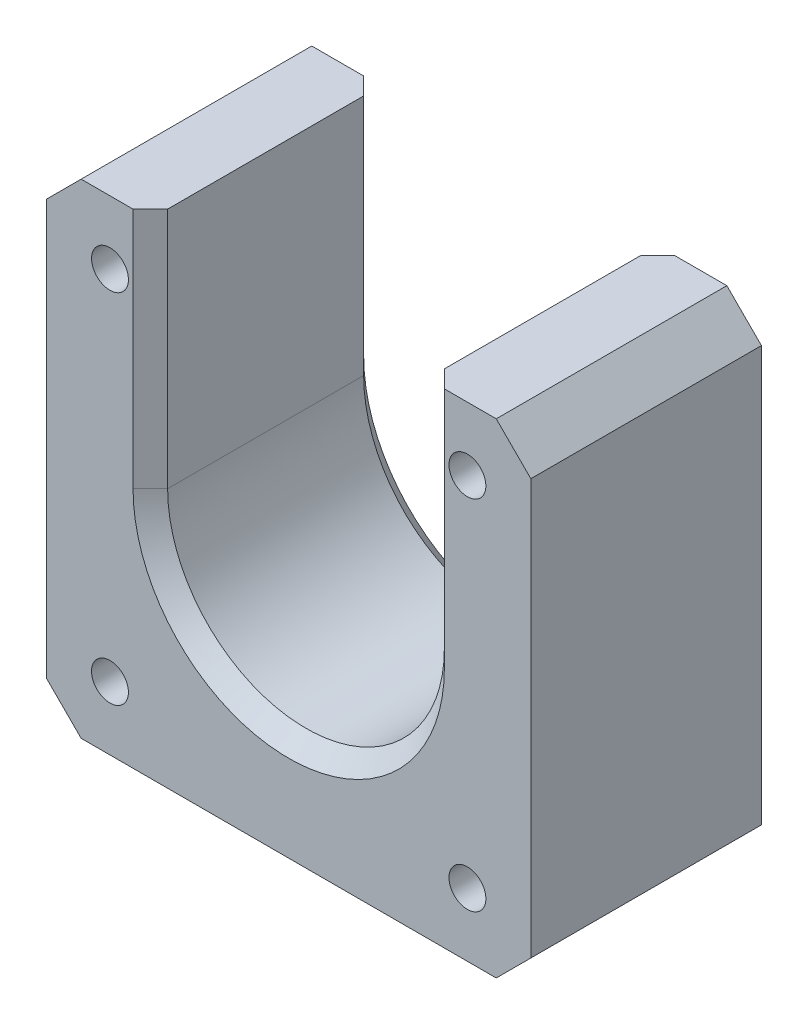
SolidWorks part; units mm, degrees
ref_plane "Front Plane" through (0, 0, 0) normal (0, 0, 1) x (1, 0, 0)
ref_plane "Top Plane" through (0, 0, 0) normal (0, 1, 0) x (1, 0, 0)
ref_plane "Right Plane" through (0, 0, 0) normal (1, 0, 0) x (0, 0, -1)
sketch "Sketch1" plane through (0, 0, 0) normal (0, 0, 1) x (1, 0, 0)
  line L1 (-21, 21) -> (21, 21)
  line L2 (-21, 21) -> (-21, -21)
  line L3 (-21, -21) -> (21, -21)
  line L4 (21, 21) -> (21, -21)
extrude "Boss-Extrude1" add sketch "Sketch1" along normal blind 20
sketch "Sketch2" plane through (0, 0, 20) normal (0, 0, 1) x (1, 0, 0)
  line L0 (-12, 0) -> (-12, 21)
  line L1 (-12, 21) -> (12, 21)
  line L2 (12, 21) -> (12, 0)
  circle A0 centre (-15.5, 15.5) radius 1.6
  circle A1 centre (15.5, -15.5) radius 1.6
  circle A3 centre (15.5, 15.5) radius 1.6
  circle A4 centre (-15.5, -15.5) radius 1.6
  arc A5 (-12, 0) -> (12, 0) centre (0, 0) ccw
extrude "Cut-Extrude1" cut sketch "Sketch2" against normal blind 30
fillet "Chamfer1" radius 3 1 edges at (-21, 21, 10) type face fillet profile chamfer first side face at (-16.5, 21, 10) second side face at (-21, 0, 10)
fillet "Chamfer2" radius 3 1 edges at (21, 21, 10) type face fillet profile chamfer first side face at (16.5, 21, 10) second side face at (21, 0, 10)
fillet "Chamfer3" radius 3 1 edges at (21, -21, 10) type face fillet profile chamfer first side face at (21, -1.5, 10) second side face at (0, -21, 10)
fillet "Chamfer4" radius 3 1 edges at (-21, -21, 10) type face fillet profile chamfer first side face at (-1.5, -21, 10) second side face at (-21, -1.5, 10)
chamfer "Chamfer6" distance 1.5 angle 45 6 edges at (-12, 10.5, 0) (12, 10.5, 0) (0, -12, 0) (-12, 10.5, 20) (12, 10.5, 20) (0, -12, 20)
